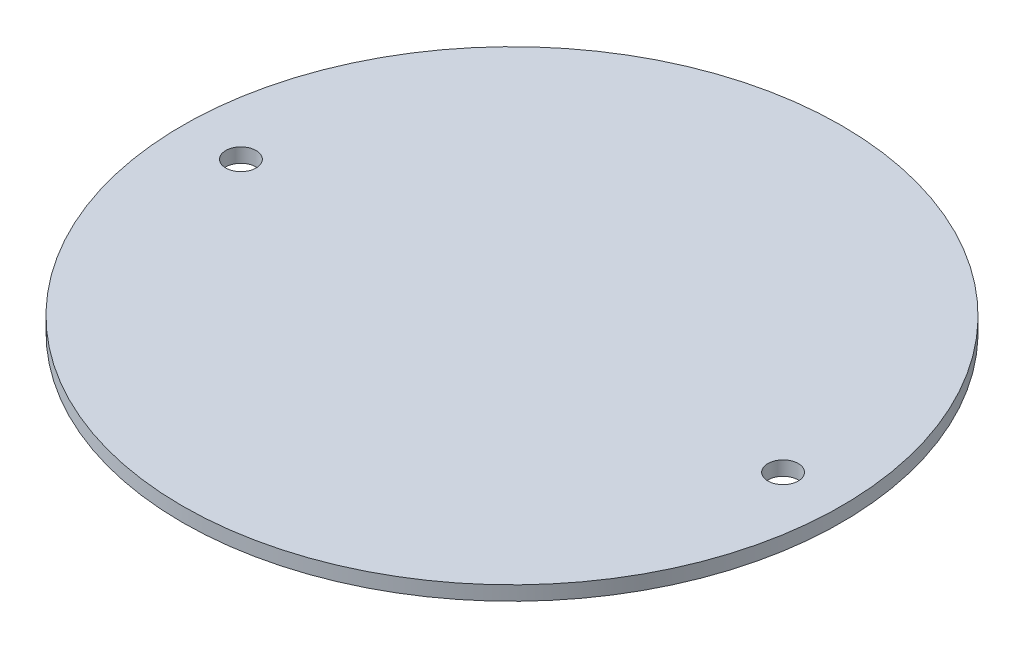
SolidWorks part; units mm, degrees
material "6061 Alloy"
ref_plane "Front Plane" through (0, 0, 0) normal (0, 0, 1) x (1, 0, 0)
ref_plane "Top Plane" through (0, 0, 0) normal (0, 1, 0) x (1, 0, 0)
ref_plane "Right Plane" through (0, 0, 0) normal (1, 0, 0) x (0, 0, -1)
sketch "Sketch2" plane through (0, 0, 0) normal (0, 1, 0) x (1, 0, 0)
  circle A0 centre (0, 0) radius 73.3425
  dimension "D1" = 146.685
extrude "Boss-Extrude1" add sketch "Sketch2" along normal blind 3.175
sketch "Sketch3" plane through (0, 3.175, 0) normal (0, 1, 0) x (1, 0, 0)
  point P0 (-60.325, 0)
  point P1 (60.325, 0)
  dimension "D1" = 60.325
  dimension "D2" = 60.325
hole_wizard "1/4 Clearance Hole1" positions "Sketch3" profile "Sketch4" hole size "1/4" standard "ANSI Inch" end condition through all
sketch "Sketch4" plane through (-60.325, 3.175, 0) normal (1, 0, 0) x (0, 0, 1)
  line L0 (0, 0) -> (0, 3.175)
  line L1 (0, 3.175) -> (3.3782, 3.175)
  line L2 (3.3782, 3.175) -> (3.3782, 0)
  line L5 (3.3782, 0) -> (0, 0)
  line L11 (0, -6.35) -> (0, 107.95) construction
  dimension "Thru Hole Dia." = 6.7564
  dimension "Thru Hole Depth" = 3.175
equation "\"outerdiameter\"= 5.775"
equation "\"D1@Sketch2\"=\"outerdiameter\""
equation "\"platethickness\"= 1 / 8"
equation "\"holespacing\"= 2.375"
equation "\"D1@Sketch3\"=\"holespacing\""
equation "\"D2@Sketch3\"=\"holespacing\""
equation "\"D1@Boss-Extrude1\"=\"platethickness\""
